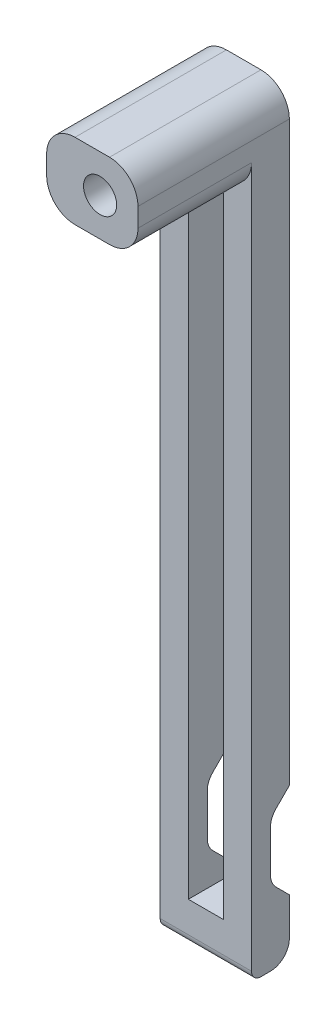
SolidWorks part; units mm, degrees
ref_plane "Ebene vorne" through (0, 0, 0) normal (0, 0, 1) x (1, 0, 0)
ref_plane "Ebene oben" through (0, 0, 0) normal (0, 1, 0) x (1, 0, 0)
ref_plane "Ebene rechts" through (0, 0, 0) normal (1, 0, 0) x (0, 0, -1)
sketch "body" plane through (0, 0, 0) normal (0, 0, 1) x (1, 0, 0)
  line L1 (-4.825, 40) -> (4.825, 40)
  line L2 (-4.825, 40) -> (-4.825, -40)
  line L3 (-4.825, -40) -> (4.825, -40)
  line L4 (4.825, 40) -> (4.825, -40)
  line L5 (-4.825, 40) -> (4.825, -40) construction
  line L6 (-4.825, -40) -> (4.825, 40) construction
  point P0 (0, 0)
  dimension "D1" = 80
  dimension "D2" = 9.65
extrude "body_" add sketch "body" along normal mid plane 4
sketch "Skizze2" plane through (0, 0, 2) normal (0, 0, 1) x (1, 0, 0)
  line L0 (0, 40) -> (0, -40) construction
  line L1 (4.825, 40) -> (-4.825, 40) construction
  line L2 (-4.825, -40) -> (4.825, -40) construction
  line L4 (-1.85, 30.75) -> (1.85, 30.75)
  line L5 (-1.85, 30.75) -> (-1.85, -35.75)
  line L6 (-1.85, -35.75) -> (1.85, -35.75)
  line L7 (1.85, 30.75) -> (1.85, -35.75)
  line L8 (-1.85, 30.75) -> (1.85, -35.75) construction
  line L9 (-1.85, -35.75) -> (1.85, 30.75) construction
  point P6 (0, -2.5)
  dimension "D1" = 66.5
  dimension "D2" = 3.7
  dimension "D3" = 37.5
extrude "rut" cut sketch "Skizze2" against normal through all
sketch "spare" plane through (4.825, 0, 0) normal (1, 0, 0) x (0, 0, -1)
  line L0 (2, -24) -> (0, -26)
  line L1 (2, -40) -> (2, 40) construction
  line L2 (0, -26) -> (0, -32)
  line L3 (0, -32) -> (2, -34)
  line L4 (2, -34) -> (2, -24)
  line L6 (2, -29) -> (-2, -29) construction
  line L7 (-2, 40) -> (-2, -40) construction
  line L8 (-2, -40) -> (2, -40) construction
  point P6 (0, -29)
  dimension "D1" = 45
  dimension "D2" = 6
  dimension "D3" = 45
  dimension "D4" = 2
  dimension "D5" = 10
  dimension "D6" = 11
extrude "notch" cut sketch "spare" against normal through all
fillet "Verrundung3" radius 2 4 edges at (-3.3375, -32, 0) (-3.3375, -26, 0) (3.3375, -26, 0) (3.3375, -32, 0)
fillet "Verrundung4" radius 1 1 edges at (0, -40, 2)
fillet "Verrundung5" radius 1 2 edges at (-3.3375, -34, -2) (-3.3375, -24, -2)
sketch "Skizze4" plane through (0, 0, 2) normal (0, 0, 1) x (1, 0, 0)
  line L0 (-4.825, 40) -> (-4.825, -39) construction
  line L1 (-4.825, 32) -> (4.825, 32)
  line L2 (-4.825, 32) -> (-4.825, 40)
  line L3 (-4.825, 40) -> (4.825, 40)
  line L4 (4.825, 32) -> (4.825, 40)
  dimension "D1" = 8
extrude "Aufsatz-Linear austragen1" add sketch "Skizze4" along normal blind 12
fillet "Verrundung6" radius 2 1 edges at (0, -40, -2)
sketch "Skizze5" plane through (0, 0, 14) normal (0, 0, 1) x (1, 0, 0)
  line L0 (4.825, 40) -> (-4.825, 40) construction
  line L1 (-4.825, 32) -> (4.825, 32) construction
  line L3 (4.825, 32) -> (4.825, 40) construction
  line L4 (-4.825, 40) -> (-4.825, 32) construction
  circle A0 centre (0.825, 36) radius 1.75
  point P5 (4.825, 36)
  dimension "D1" = 8
  dimension "D5" = 3.5
  dimension "D2" = 4
  dimension "D3" = 5.65
  dimension "D4" = 4
extrude "loch" cut sketch "Skizze5" against normal through all
fillet "Verrundung7" radius 3 4 edges at (-4.825, 40, 6) (4.825, 40, 6) (-4.825, 32, 8) (4.825, 32, 8)
